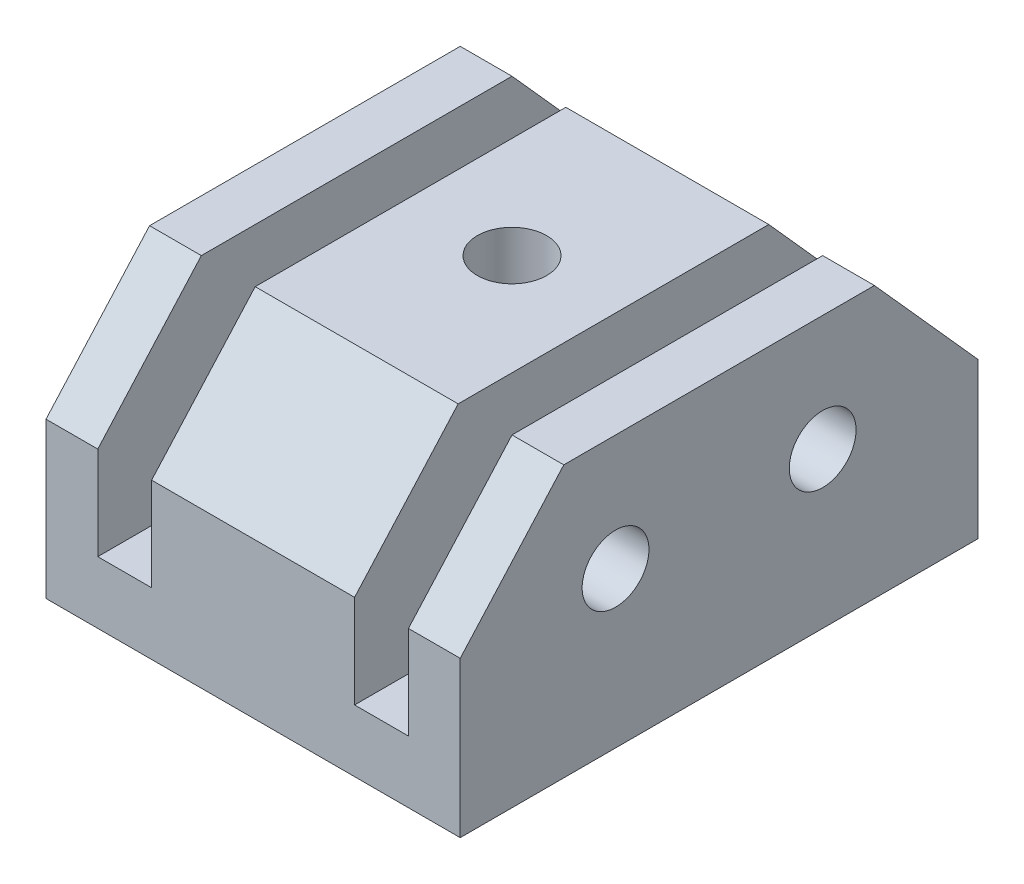
SolidWorks part; units mm, degrees
ref_plane "Front Plane" through (0, 0, 0) normal (0, 0, 1) x (1, 0, 0)
ref_plane "Top Plane" through (0, 0, 0) normal (0, 1, 0) x (1, 0, 0)
ref_plane "Right Plane" through (0, 0, 0) normal (1, 0, 0) x (0, 0, -1)
sketch "Sketch1" plane through (0, 0, 0) normal (1, 0, 0) x (0, 0, -1)
  line L1 (0, 0) -> (63.5, 0)
  line L2 (0, 0) -> (0, 6.35)
  line L3 (0, 6.35) -> (63.5, 6.35)
  line L4 (63.5, 0) -> (63.5, 6.35)
  dimension "D1" = 6.35
  dimension "D2" = 63.5
extrude "Boss-Extrude1" add sketch "Sketch1" against normal blind 50.8
sketch "Sketch2" plane through (0, 0, 0) normal (1, 0, 0) x (0, 0, -1)
  line L0 (0, 6.35) -> (0, 19.05)
  line L1 (0, 19.05) -> (12.7, 33.249)
  line L2 (12.7, 33.249) -> (50.8, 33.249)
  line L3 (50.8, 33.249) -> (63.5, 19.05)
  line L4 (63.5, 19.05) -> (63.5, 6.35)
  line L5 (63.5, 6.35) -> (0, 6.35)
  point P7 (31.75, 33.249)
  point P10 (31.75, 6.35)
  dimension "D1" = 38.1
  dimension "D2" = 12.7
  dimension "D3" = 12.7
  dimension "D4" = 19.05
  dimension "D5" = 19.05
extrude "Boss-Extrude2" add sketch "Sketch2" against normal blind 50.8
sketch "Sketch10" plane through (0, 0, -63.5) normal (0, 0, -1) x (-1, 0, 0)
  line L1 (50.8, 33.249) -> (0, 33.249) construction
  line L3 (6.35, 7.62) -> (6.35, 33.249)
  line L4 (6.35, 33.249) -> (12.954, 33.249)
  line L5 (12.954, 7.62) -> (12.954, 33.249)
  line L6 (6.35, 7.62) -> (12.954, 7.62)
  line L8 (50.8, 0) -> (0, 0) construction
  point P11 (12.954, 7.62)
  dimension "D1" = 7.62
  dimension "D2" = 6.604
  dimension "D3" = 6.35
extrude "Cut-Extrude1" cut sketch "Sketch10" against normal through all
pattern_linear "LPattern3" count 2 spacing 31.496 along (-1, 0, 0) of "Cut-Extrude1"
sketch "Sketch11" plane through (0, 0, 0) normal (1, 0, 0) x (0, 0, -1)
  circle A0 centre (19.05, 19.05) radius 4.0957
  circle A1 centre (19.05, 19.05) radius 7.9375 construction
  circle A2 centre (44.45, 19.05) radius 4.0958
  circle A3 centre (44.45, 19.05) radius 7.9375 construction
  dimension "D1" = 8.1915
  dimension "D3" = 15.875
  dimension "D4" = 8.1915
  dimension "D6" = 15.875
  dimension "D2" = 6.35
  dimension "D5" = 6.35
extrude "Cut-Extrude2" cut sketch "Sketch11" against normal through all
sketch "Sketch14" plane through (0, 33.249, 0) normal (0, 1, 0) x (1, 0, 0)
  line L3 (-37.846, 12.7) -> (-37.846, 50.8) construction
  point P0 (-25.4, 31.75)
  point P4 (-37.846, 31.75)
  dimension "D1" = 12.446
sketch "Sketch17" plane through (0, 40.0201, -44.7438) normal (0, 0.6667, -0.7454) x (-1, 0, 0)
  line L0 (12.954, -28.1343) -> (12.954, -9.0843) construction
  line L1 (37.846, -9.0843) -> (12.954, -9.0843) construction
  point P0 (25.4, -18.6093)
  point P4 (12.954, -18.6093)
  point P7 (25.4, -9.0843)
sketch "Sketch18" plane through (0, 8.4667, 9.466) normal (0, 0.6667, 0.7454) x (1, 0, 0)
  line L0 (-12.954, 33.249) -> (-12.954, 14.199) construction
  line L1 (-37.846, 33.249) -> (-12.954, 33.249) construction
  point P0 (-25.4, 23.724)
  point P1 (-25.4, 23.724)
  point P4 (-12.954, 23.724)
  point P7 (-25.4, 33.249)
ref_plane "Plane2" through (0, 33.02, 0) normal (0, -1, 0) x (-1, 0, 0)
fillet "Fillet1" [suppressed] radius 2.54
sketch "Sketch19" plane through (0, 0, 0) normal (0, -1, 0) x (1, 0, 0)
  line L0 (-24.6552, -63.5) -> (-24.6552, 0) construction
  line L1 (-50.8, -63.5) -> (0, -63.5) construction
  line L2 (-50.8, 0) -> (0, 0) construction
  line L3 (0, -31.75) -> (-50.8, -31.75) construction
  line L4 (0, 0) -> (0, -63.5) construction
  line L5 (-50.8, 0) -> (-50.8, -63.5) construction
  line L7 (-3.4052, -53) -> (-45.9052, -53)
  line L8 (-3.4052, -53) -> (-3.4052, -10.5)
  line L9 (-3.4052, -10.5) -> (-45.9052, -10.5)
  line L10 (-45.9052, -53) -> (-45.9052, -10.5)
  line L11 (-3.4052, -53) -> (-45.9052, -10.5) construction
  line L12 (-3.4052, -10.5) -> (-45.9052, -53) construction
  point P12 (-24.6552, -31.75)
  dimension "D1" = 42.5
extrude "Cut-Extrude3" cut sketch "Sketch19" against normal blind 5.08
sketch "Sketch21" plane through (0, 0, 0) normal (0, -1, 0) x (1, 0, 0)
  line L0 (-25.4, -63.5) -> (-25.4, 0) construction
  line L1 (-50.8, -63.5) -> (0, -63.5) construction
  line L2 (-50.8, 0) -> (0, 0) construction
  line L3 (-50.8, -31.75) -> (0, -31.75) construction
  line L4 (-50.8, 0) -> (-50.8, -63.5) construction
  line L5 (0, 0) -> (0, -63.5) construction
  circle A0 centre (-40.9, -47.25) radius 1.7
  circle A1 centre (-40.9, -16.25) radius 1.7
  circle A2 centre (-9.9, -16.25) radius 1.7
  circle A3 centre (-9.9, -47.25) radius 1.7
  point P14 (-25.4, -31.75)
  point P24 (-25.4, -31.75)
  dimension "D1" = 3.4
  dimension "D3" = 15.5
  dimension "D2" = 15.5
  dimension "D4" = 4
extrude "Cut-Extrude4" cut sketch "Sketch21" against normal up to next
sketch "Sketch22" plane through (0, 0, 0) normal (0, -1, 0) x (1, 0, 0)
  line L1 (-25.4, -63.5) -> (-25.4, 0) construction
  line L2 (-50.8, -63.5) -> (0, -63.5) construction
  line L3 (-50.8, 0) -> (0, 0) construction
  line L4 (0, -31.75) -> (-50.8, -31.75) construction
  line L6 (0, 0) -> (0, -63.5) construction
  line L7 (-50.8, 0) -> (-50.8, -63.5) construction
  circle A1 centre (-25.4, -31.75) radius 11
  dimension "D1" = 22
extrude "Cut-Extrude5" cut sketch "Sketch22" against normal blind 2.032 from surface starting at face at (-9.9, 5.08, -48.95)
sketch "Sketch23" plane through (0, 0, 0) normal (0, -1, 0) x (1, 0, 0)
  circle A0 centre (-25.4, -31.75) radius 4.25
extrude "Cut-Extrude6" cut sketch "Sketch23" against normal through all
